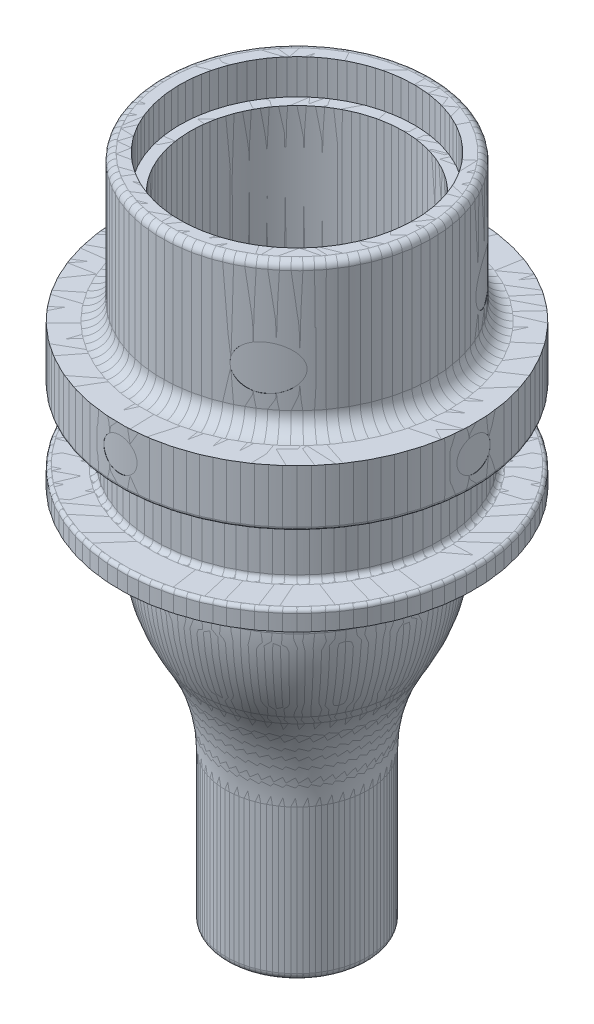
SolidWorks part; units mm, degrees
other "Spun Profile"
other "SwirlInner"
material "Brass"
ref_plane "Front Plane" through (0, 0, 0) normal (0, 0, 1) x (1, 0, 0)
ref_plane "Top Plane" through (0, 0, 0) normal (0, 1, 0) x (1, 0, 0)
ref_plane "Right Plane" through (0, 0, 0) normal (1, 0, 0) x (0, 0, -1)
sketch "Sketch1" plane through (0, 0, 0) normal (0, 0, 1) x (1, 0, 0)
  line L0 (4.826, 23.876) -> (4.826, 18.6563)
  line L2 (6.3373, 17.3228) -> (6.3373, 16.7513)
  line L3 (6.3373, 13.5128) -> (5.0673, 13.5128)
  line L5 (4.445, 10.4116) -> (2.54, 7.112)
  line L6 (2.54, 7.112) -> (2.54, 0)
  line L7 (2.54, 0) -> (2.032, 0)
  line L8 (2.032, 0) -> (2.032, 7.332)
  line L9 (2.032, 7.332) -> (3.81, 10.4116)
  line L10 (3.81, 10.4116) -> (3.81, 22.6314)
  line L11 (4.191, 23.876) -> (4.826, 23.876)
  line L12 (0, 20.955) -> (0, 0) construction
  line L13 (6.2103, 16.6243) -> (5.2578, 16.6243)
  line L14 (5.08, 16.4465) -> (5.08, 14.3891)
  line L15 (5.2578, 14.2113) -> (6.2103, 14.2113)
  line L16 (5.08, 13.5128) -> (5.08, 17.3228) construction
  line L17 (6.3373, 14.0843) -> (6.3373, 13.5128)
  line L18 (5.0673, 13.5128) -> (4.445, 13.5128)
  line L19 (4.445, 13.5128) -> (4.445, 10.4116)
  line L20 (6.3373, 17.3228) -> (6.3373, 18.6563)
  line L21 (6.3373, 18.6563) -> (4.826, 18.6563)
  line L22 (4.191, 23.876) -> (4.191, 22.6314)
  line L23 (4.191, 22.6314) -> (3.81, 22.6314)
  arc A0 (6.2103, 14.2113) -> (6.3373, 14.0843) centre (6.2103, 14.0843) cw
  arc A1 (6.2103, 16.6243) -> (6.3373, 16.7513) centre (6.2103, 16.7513) ccw
  arc A2 (5.08, 14.3891) -> (5.2578, 14.2113) centre (5.2578, 14.3891) ccw
  arc A3 (5.2578, 16.6243) -> (5.08, 16.4465) centre (5.2578, 16.4465) ccw
  point P20 (5.08, 15.4178)
  point P36 (6.3373, 14.2113)
  point P41 (5.08, 14.2113)
  point P44 (5.08, 16.6243)
  dimension "D14" = 0.127
  dimension "D15" = 0.1778
  dimension "D1" = 6.3373
  dimension "D3" = 0.6985
  dimension "D4" = 7.112
  dimension "D5" = 0.508
  dimension "D6" = 30
  dimension "D7" = 10.3632
  dimension "D8" = 2.54
  dimension "D9" = 1.27
  dimension "D10" = 2.413
  dimension "D11" = 5.08
  dimension "D12" = 0.635
  dimension "D13" = 150
  dimension "D16" = 20.955
  dimension "D17" = 1.016
  dimension "D18" = 3.81
  dimension "D19" = 2.032
  dimension "D20" = 1.2446
  dimension "D21" = 0.381
  dimension "D22" = 23.876
  dimension "D23" = 2.032
revolve "Revolve1" add sketch "Sketch1" angle 360 about L12
sketch "Sketch2" plane through (0, 0, 0) normal (0, 0, 1) x (1, 0, 0)
  line L0 (3.81, 23.876) -> (-3.81, 23.876) construction
  point P0 (2.794, 20.574)
  dimension "D1" = 3.302
  dimension "D2" = 2.794
hole_wizard "1/16 (0.0625) Diameter Hole1" positions "Sketch2" profile "Sketch3" hole size "1/16" standard "ANSI Inch" end condition through all
sketch "Sketch3" plane through (2.794, 20.574, 0) normal (1, 0, 0) x (0, 1, 0)
  line L0 (0, 0) -> (0, 6.3373)
  line L1 (0, 6.3373) -> (0.7937, 6.3373)
  line L2 (0.7937, 6.3373) -> (0.7937, 0)
  line L5 (0.7937, 0) -> (0, 0)
  line L11 (0, -6.35) -> (0, 107.95) construction
  dimension "Thru Hole Dia." = 1.5875
  dimension "Thru Hole Depth" = 6.3373
pattern_circular "CirPattern1" count 4 over 360 about axis through (0, 20.955, 0) along (0, 1, 0) of "1/16 (0.0625) Diameter Hole1" reverse direction yes
ref_plane "Plane1" through (0, 0, 6.3373) normal (0, 0, 1) x (1, 0, 0)
sketch "Sketch5" plane through (0, 0, 6.3373) normal (0, 0, 1) x (1, 0, 0)
  line L0 (0, 16.7513) -> (0, 18.6563) construction
  line L1 (6.3373, 18.6563) -> (-6.3373, 18.6563) construction
  line L2 (-6.3373, 16.7513) -> (6.3373, 16.7513) construction
  point P0 (0, 17.7038)
  point P8 (0, 17.7038)
hole_wizard "#0-80 Tapped Hole1" positions "Sketch5" profile "Sketch7" tap size "#0-80" standard "ANSI Inch"
sketch "Sketch7" plane through (0, 17.7038, 6.3373) normal (1, 0, 0) x (0, -1, 0)
  line L0 (0, 0) -> (0, 2.1359)
  line L1 (0, 2.1359) -> (0.5956, 1.778)
  line L2 (0.5956, 1.778) -> (0.5956, 0)
  line L5 (0.5956, 0) -> (0, 0)
  line L10 (0, 2.1359) -> (-0.5956, 1.778) construction
  line L11 (0, -6.35) -> (0, 107.95) construction
  dimension "Tap Drill Dia." = 1.1913
  dimension "Tap Drill Depth" = 1.778
  dimension "Drill Angle" = 118
cosmetic thread "Hole Thread2" parameters "D1"=1.778, "D2"=1.524
pattern_circular "CirPattern2" count 4 over 360 about axis through (0, 20.955, 0) along (0, 1, 0) of "#0-80 Tapped Hole1" reverse direction yes
cosmetic thread "Hole Thread3" parameters "D1"=1.778, "D2"=1.524
cosmetic thread "Hole Thread4" parameters "D1"=1.778, "D2"=1.524
cosmetic thread "Hole Thread5" parameters "D1"=1.778, "D2"=1.524
fillet "Fillet1" radius 0.254 1 edges at (-4.826, 23.876, 0)
fillet "Fillet2" radius 6.35 2 edges at (-3.81, 10.4116, 0) (-2.032, 7.332, 0)
fillet "Fillet3" radius 6.35 2 edges at (-4.445, 10.4116, 0) (-2.54, 7.112, 0)
fillet "Fillet4" radius 0.635 1 edges at (-4.826, 18.6563, 0)
fillet "Fillet5" radius 0.254 2 edges at (-2.032, 0, 0) (-2.54, 0, 0)
fillet "Fillet6" radius 0.762 1 edges at (-4.445, 13.5128, 0)
ref_plane "Plane2" through (0, 20.955, 0) normal (1, 0, 0) x (0, 1, 0)
sketch "Spun Profile Sketch2" plane through (0, 20.955, 0) normal (1, 0, 0) x (0, 1, 0)
  line L0 (-4.3307, 6.2103) -> (-4.3307, 5.2578)
  line L1 (-4.5085, 5.08) -> (-6.5659, 5.08)
  line L2 (-6.7437, 5.2578) -> (-6.7437, 6.2103)
  line L3 (-6.8707, 6.3373) -> (-7.4422, 6.3373)
  line L4 (-7.4422, 6.3373) -> (-7.4422, 5.207)
  line L5 (-8.2042, 4.445) -> (-8.842, 4.445)
  line L6 (-12.017, 3.5943) -> (-12.3695, 3.3907)
  line L7 (-15.5445, 2.54) -> (-20.701, 2.54)
  line L8 (-20.701, 2.032) -> (-15.3245, 2.032)
  line L9 (-12.1495, 2.8827) -> (-12.017, 2.9593)
  line L10 (-8.842, 3.81) -> (1.6764, 3.81)
  line L11 (1.6764, 3.81) -> (1.6764, 4.191)
  line L12 (1.6764, 4.191) -> (2.921, 4.191)
  line L13 (2.921, 4.191) -> (2.921, 4.572)
  line L14 (2.667, 4.826) -> (-1.6637, 4.826)
  line L15 (-2.2987, 5.461) -> (-2.2987, 6.3373)
  line L16 (-2.2987, 6.3373) -> (-4.2037, 6.3373)
  line L17 (0, 0) -> (1000, 0) construction
  arc A0 (-4.2037, 6.3373) -> (-4.3307, 6.2103) centre (-4.2037, 6.2103) ccw
  arc A1 (-4.3307, 5.2578) -> (-4.5085, 5.08) centre (-4.5085, 5.2578) cw
  arc A2 (-6.5659, 5.08) -> (-6.7437, 5.2578) centre (-6.5659, 5.2578) cw
  arc A3 (-6.7437, 6.2103) -> (-6.8707, 6.3373) centre (-6.8707, 6.2103) ccw
  arc A4 (-7.4422, 5.207) -> (-8.2042, 4.445) centre (-8.2042, 5.207) cw
  arc A5 (-8.842, 4.445) -> (-12.017, 3.5943) centre (-8.842, -1.905) ccw
  arc A6 (-12.3695, 3.3907) -> (-15.5445, 2.54) centre (-15.5445, 8.89) cw
  arc A7 (-20.701, 2.54) -> (-20.701, 2.032) centre (-20.701, 2.286) ccw
  arc A8 (-15.3245, 2.032) -> (-12.1495, 2.8827) centre (-15.3245, 8.382) ccw
  arc A9 (-12.017, 2.9593) -> (-8.842, 3.81) centre (-8.842, -2.54) cw
  arc A10 (2.921, 4.572) -> (2.667, 4.826) centre (2.667, 4.572) ccw
  arc A11 (-1.6637, 4.826) -> (-2.2987, 5.461) centre (-1.6637, 5.461) cw
revolve "Revolve" add sketch "Spun Profile Sketch2" angle 360 about L17
ref_plane "FrontFace" through (0, -0.254, 0) normal (0, -1, 0) x (-1, 0, 0)
